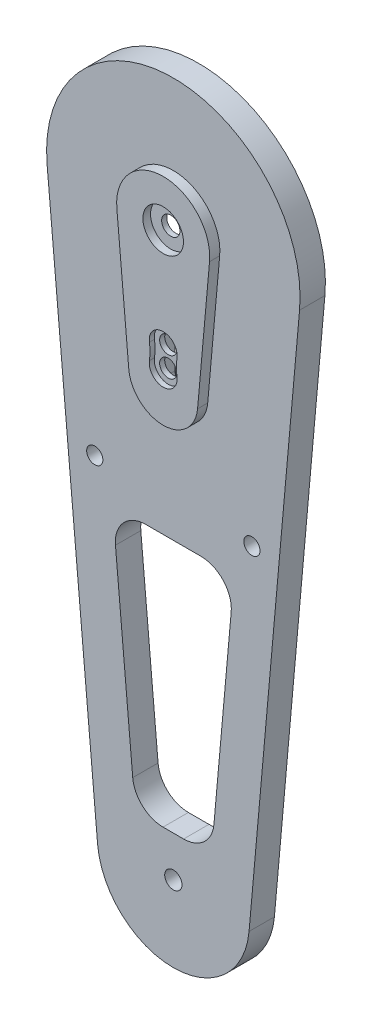
SolidWorks part; units mm, degrees
material "PLA"
ref_plane "Alzado" through (0, 0, 0) normal (0, 0, 1) x (1, 0, 0)
ref_plane "Planta" through (0, 0, 0) normal (0, 1, 0) x (1, 0, 0)
ref_plane "Vista lateral" through (0, 0, 0) normal (1, 0, 0) x (0, 0, -1)
other "PLA"
sketch "Croquis1" plane through (0, 0, 0) normal (0, 0, 1) x (1, 0, 0)
  line L0 (0, 112) -> (0, 0) construction
  line L1 (-14.9401, -1.3393) -> (-25.1002, 112)
  line L2 (14.9401, -1.3393) -> (24.9002, 109.7679)
  line L3 (0, 119.505) -> (19.4147, 119.505) construction
  line L4 (-3.65, 83.155) -> (-3.65, 101.0409)
  line L5 (3.65, 83.155) -> (3.65, 101.0409)
  line L11 (0, 112) -> (0, 123.4883) construction
  line L12 (0.5, 119.4883) -> (0.5, 119.505)
  arc A0 (-14.9401, -1.3393) -> (14.9401, -1.3393) centre (0, 0) ccw
  arc A1 (24.9002, 109.7679) -> (-24.9002, 109.7679) centre (0, 112) ccw
  circle A2 centre (0, 112) radius 7.505
  circle A3 centre (0, 0) radius 1.7
  circle A4 centre (0, 112) radius 1.75
  arc A5 (0, 79.505) -> (-3.65, 83.155) centre (0, 83.155) cw
  arc A6 (-5.8522, 107.3014) -> (-3.65, 101.0409) centre (-13.65, 101.0409) cw
  arc A7 (5.8522, 107.3014) -> (3.65, 101.0409) centre (13.65, 101.0409) ccw
  arc A8 (0, 79.505) -> (3.65, 83.155) centre (0, 83.155) ccw
  point P26 (0, 79.4404)
  dimension "D1" = 30
  dimension "D2" = 50
  dimension "D4" = 15.01
  dimension "D5" = 3.4
  dimension "D6" = 3.5
  dimension "D7" = 10
  dimension "D3" = 112
  dimension "D8" = 40
  dimension "D9" = 7.3
extrude "Saliente-Extruir1" add sketch "Croquis1" along normal blind 5 contours L2 A1 L1 A0 A2 A3 | A0 region at (0, 64.8201, 0)
ref_plane "Plano1" through (0, 0, 0) normal (1, 0, 0) x (0, -1, 0)
sketch "Croquis11" plane through (0, 0, 0) normal (0, 0, -1) x (-1, 0, 0)
  line L2 (0, 0) -> (0, 137) construction
  line L3 (-10.6804, 11.0037) -> (-15.5, 64.7681) construction
  line L4 (-14.9401, -1.3393) -> (-24.9002, 109.7679) construction
  arc A2 (24.9002, 109.7679) -> (-24.9002, 109.7679) centre (0, 112) ccw construction
  circle A3 centre (-15.5, 64.7681) radius 1.6
  circle A4 centre (15.5, 64.7681) radius 1.6
  dimension "D1" = 31
extrude "Cortar-Extruir1" cut sketch "Croquis11" against normal blind 6 contours A3 | A4
sketch "Croquis12" plane through (0, 0, 5) normal (0, 0, 1) x (1, 0, 0)
  line L0 (0, 79.5266) -> (0, 0) construction
  line L1 (-12, 58) -> (12, 58)
  line L2 (12, 58) -> (7.5178, 8)
  line L3 (7.5178, 8) -> (-7.5178, 8)
  line L4 (-12, 58) -> (-7.5178, 8)
  line L5 (14.9401, -1.3393) -> (24.9002, 109.7679) construction
  point P8 (0, 8)
  point P9 (0, 58)
  dimension "D1" = 24
  dimension "D2" = 50
  dimension "D3" = 8
extrude "Cortar-Extruir2" cut sketch "Croquis12" against normal up to next contours L4 | L0 L3 | L0 L3 | L2 | L1 L0 | L0 L1 region at (4.9652, 34.9137, 5) region at (-4.9652, 34.9137, 5)
sketch "Croquis13" plane through (0, 0, 5) normal (0, 0, 1) x (1, 0, 0)
  line L0 (0, 137) -> (0, -15) construction
  line L2 (6.7847, 84.8645) -> (9.1438, 111.1803)
  line L3 (-6.7847, 84.8645) -> (-9.1438, 111.1803)
  line L4 (14.9401, -1.3393) -> (24.9002, 109.7679) construction
  arc A0 (-9.1438, 111.1803) -> (9.1438, 111.1803) centre (0, 112) ccw
  arc A2 (24.9002, 109.7679) -> (-24.9002, 109.7679) centre (0, 112) ccw construction
  arc A3 (-14.9401, -1.3393) -> (14.9401, -1.3393) centre (0, 0) ccw construction
  arc A4 (-9.1438, 111.1803) -> (9.1438, 111.1803) centre (0, 112) cw
  arc A5 (5.8522, 107.3014) -> (-5.8522, 107.3014) centre (0, 112) ccw construction
  arc A6 (6.7847, 84.8645) -> (-6.7847, 84.8645) centre (0, 85.4727) cw
  circle A7 centre (0, 112) radius 4
  circle A8 centre (0, 112) radius 1.8
  dimension "D1" = 8
  dimension "D2" = 3.6
extrude "Saliente-Extruir2" add sketch "Croquis13" along normal blind 2 contours A6 L3 A4 L2 | A8
extrude "Saliente-Extruir3" add sketch "Croquis13<3>" against normal blind 0.5 contours L0 A7 | A7 | A8 region at (-1.9347, 112, 5)
sketch "Croquis13<3>" plane through (0, 0, 5) normal (0, 0, 1) x (1, 0, 0) same geometry as "Croquis13"
sketch "Croquis14" plane through (0, 0, 7) normal (0, 0, 1) x (1, 0, 0)
  circle A0 centre (0, 112) radius 4
  dimension "D1" = 8
extrude "Cortar-Extruir3" cut sketch "Croquis14" against normal blind 1.5
chamfer "Chaflán1" distance 1 angle 45 6 edges at (0, 79.505, 0) (-3.65, 92.0979, 0) (3.65, 92.0979, 0) (4.2166, 104.3592, 0) (-4.2166, 104.3592, 0) (0, 119.505, 0)
sketch "Croquis15" plane through (0, 0, 5) normal (0, 0, -1) x (-1, 0, 0)
  line L0 (0, 137) -> (0, -15) construction
  arc A0 (24.9002, 109.7679) -> (-24.9002, 109.7679) centre (0, 112) ccw construction
  arc A1 (-14.9401, -1.3393) -> (14.9401, -1.3393) centre (0, 0) ccw construction
  circle A2 centre (0, 87.915) radius 1.45
  circle A3 centre (0, 91.915) radius 1.45
  arc A4 (-3.65, 83.155) -> (3.65, 83.155) centre (0, 83.155) ccw construction
  circle A5 centre (0, 91.915) radius 0.75
  circle A6 centre (0, 87.915) radius 0.75
  point P15 (0, 79.505)
  dimension "D1" = 8.41
  dimension "D3" = 2.9
  dimension "D4" = 1.5
  dimension "D2" = 4
hole_wizard "Refrentado para tornillo con cabeza troncocónica de M31" positions "Croquis16" profile "Croquis17" counterbore size "M3" standard "Ansi Metric" end condition up to next
sketch "Croquis16" plane through (0, 0, 7) normal (0, 0, -1) x (-1, 0, 0)
  point P0 (0, 91.915)
  point P3 (0, 87.915)
sketch "Croquis17" plane through (0, 91.915, 7) normal (1, 0, 0) x (0, -1, 0)
  line L0 (0, 0) -> (0, 2)
  line L1 (0, 2) -> (1.7, 2)
  line L3 (1.7, 2) -> (1.7, 1)
  line L4 (1.7, 1) -> (2.75, 1)
  line L5 (2.75, 1) -> (2.75, 0)
  line L7 (2.75, 0) -> (0, 0)
  line L11 (0, -6.35) -> (0, 107.95) construction
  dimension "Diámetro de taladro hasta el siguiente" = 3.4
  dimension "Profundidad de taladro hasta el siguiente" = 2
  dimension "Diámetro de refrentado" = 5.5
  dimension "Profundidad de refrentado" = 1
fillet "Redondeo1" radius 10 2 edges at (-1.8875, 89.915, 6.5) (1.8875, 89.915, 6.5)
fillet "Redondeo2" radius 6 4 edges at (7.5178, 8, 2.5) (-7.5178, 8, 2.5) (12, 58, 2.5) (-12, 58, 2.5)
